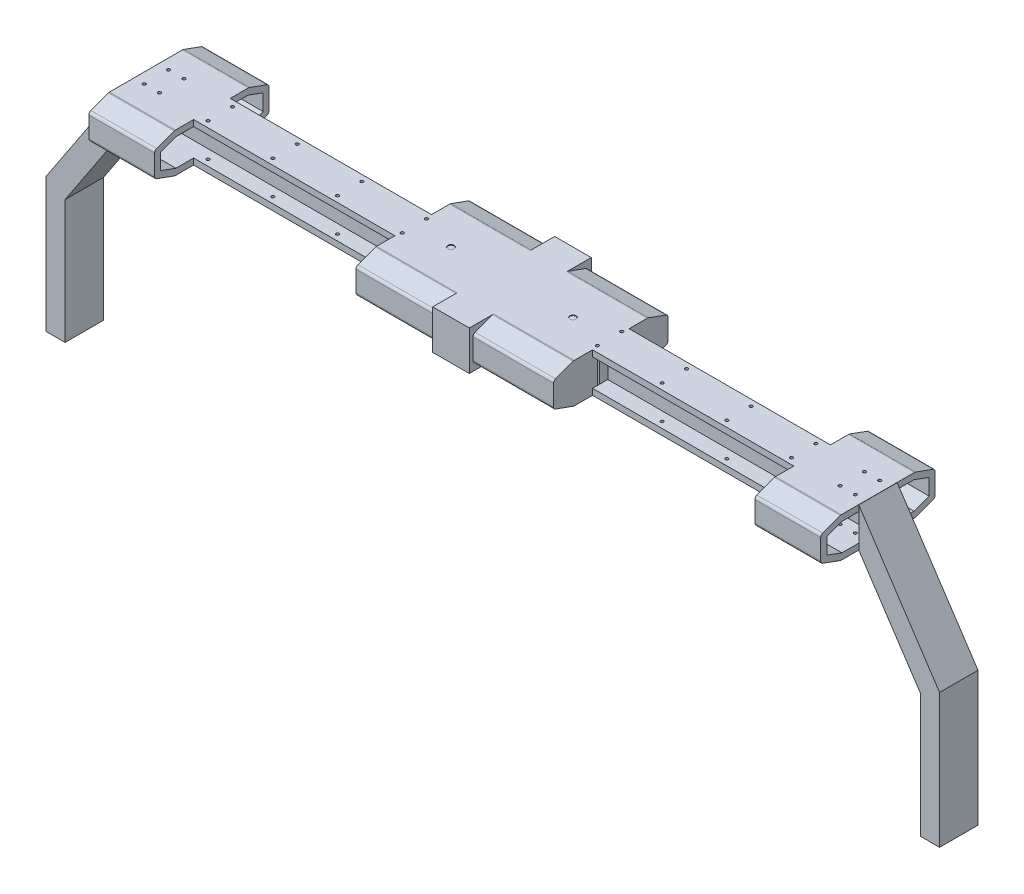
SolidWorks part; units mm, degrees
ref_plane "Alzado" through (0, 0, 0) normal (0, 0, 1) x (1, 0, 0)
ref_plane "Planta" through (0, 0, 0) normal (0, 1, 0) x (1, 0, 0)
ref_plane "Vista lateral" through (0, 0, 0) normal (1, 0, 0) x (0, 0, -1)
sketch "Sketch1" plane through (0, 0, 0) normal (1, 0, 0) x (0, 0, -1)
  line L0 (0, 0) -> (0, 59.5014) construction
  line L1 (0, 0) -> (-76.3871, 0) construction
  line L2 (30, 32.315) -> (-30, 32.315)
  line L3 (-30, 32.315) -> (-30, 22.315)
  line L4 (-30, 22.315) -> (-5, 22.315)
  line L5 (-5, 22.315) -> (-5, -22.315)
  line L6 (5, 22.315) -> (5, -22.315)
  line L7 (30, 22.315) -> (5, 22.315)
  line L8 (30, 32.315) -> (30, 22.315)
  line L9 (30, -32.315) -> (30, -22.315)
  line L10 (30, -22.315) -> (5, -22.315)
  line L11 (-30, -22.315) -> (-5, -22.315)
  line L12 (-30, -32.315) -> (-30, -22.315)
  line L13 (30, -32.315) -> (-30, -32.315)
  point P13 (0, 32.315)
  point P16 (5, 0)
  point P17 (-5, 0)
  point P19 (0, -32.315)
  dimension "D1" = 5
  dimension "D2" = 10
  dimension "D3" = 30
  dimension "D4" = 32.315
extrude "Boss-Extrude1" add sketch "Sketch1" along normal blind 600
sketch "Sketch10" plane through (0, 0, 0) normal (0, 1, 0) x (1, 0, 0)
  line L0 (0, 30) -> (0, -30) construction
  line L1 (0, 100) -> (30, 100)
  line L2 (0, 100) -> (0, -100)
  line L3 (0, -100) -> (30, -100)
  line L4 (30, 100) -> (30, -100)
  point P4 (30, 0)
  dimension "D1" = 30
  dimension "D2" = 200
extrude "Boss-Extrude5" add sketch "Sketch10" along normal mid plane 52
sketch "Sketch6" plane through (0, 32.315, 0) normal (0, 1, 0) x (1, 0, 0)
  line L0 (0, 30) -> (0, -30) construction
  line L1 (0, 100) -> (30, 100)
  line L2 (0, 100) -> (0, -100)
  line L3 (0, -100) -> (30, -100)
  line L4 (30, 100) -> (30, -100)
  point P4 (30, 0)
  dimension "D1" = 200
  dimension "D2" = 30
extrude "Boss-Extrude3" add sketch "Sketch6" against normal up to surface (64.63 mm away) up to face at (300, -32.315, 0)
ref_plane "Plane3" through (30, 0, 0) normal (1, 0, 0) x (0, 0, -1)
sketch "Sketch7" plane through (30, 0, 0) normal (1, 0, 0) x (0, 0, -1)
  line L0 (-30, -32.315) -> (30, -32.315) construction
  line L1 (0, 0) -> (58.0683, 0) construction
  line L2 (59.9268, 32.315) -> (-59.9268, 32.315)
  line L3 (93.88, -5.2694) -> (93.88, 16.7769)
  line L4 (90.5901, 21.4754) -> (61.6369, 32.0135)
  line L5 (90.5901, -21.4754) -> (61.6369, -32.0135)
  line L6 (93.88, 5.2694) -> (93.88, -16.7769)
  line L7 (59.9268, -32.315) -> (-59.9268, -32.315)
  line L8 (0, 0) -> (0, 18.5009) construction
  line L9 (-93.88, 5.2694) -> (-93.88, -16.7769)
  line L10 (-90.5901, -21.4754) -> (-61.6369, -32.0135)
  line L11 (-90.5901, 21.4754) -> (-61.6369, 32.0135)
  line L12 (-93.88, -5.2694) -> (-93.88, 16.7769)
  arc A0 (93.88, -16.7769) -> (90.5901, -21.4754) centre (88.88, -16.7769) cw
  arc A1 (59.9268, -32.315) -> (60.7951, -32.239) centre (59.9268, -27.315) ccw
  arc A2 (60.7951, -32.239) -> (61.6369, -32.0135) centre (60.6047, -29.845) ccw
  arc A3 (60.7951, 32.239) -> (61.6369, 32.0135) centre (60.6047, 29.845) cw
  arc A4 (59.9268, 32.315) -> (60.7951, 32.239) centre (59.9268, 27.315) cw
  arc A5 (93.88, 16.7769) -> (90.5901, 21.4754) centre (88.88, 16.7769) ccw
  arc A6 (-93.88, 16.7769) -> (-90.5901, 21.4754) centre (-88.88, 16.7769) cw
  arc A7 (-59.9268, 32.315) -> (-60.7951, 32.239) centre (-59.9268, 27.315) ccw
  arc A8 (-60.7951, 32.239) -> (-61.6369, 32.0135) centre (-60.6047, 29.845) ccw
  arc A9 (-60.7951, -32.239) -> (-61.6369, -32.0135) centre (-60.6047, -29.845) cw
  arc A10 (-59.9268, -32.315) -> (-60.7951, -32.239) centre (-59.9268, -27.315) cw
  arc A11 (-93.88, -16.7769) -> (-90.5901, -21.4754) centre (-88.88, -16.7769) ccw
  point P42 (0, -32.315)
  point P44 (0, 32.315)
  dimension "D1" = 0
extrude "Boss-Extrude4" add sketch "Sketch7" along normal blind 132 contours L9 A11 L10 A9 A10 L7 A1 A2 L5 A0 L6 L3 A5 L4 A3 A4 L2 A7 A8 L11 A6 L12 region at (30, 0, 0)
sketch "Sketch8" plane through (600, 0, 0) normal (1, 0, 0) x (0, 0, -1)
  line L0 (-30, -32.315) -> (30, -32.315) construction
  line B0 (0, 0) -> (58.0683, 0) construction
  line B1 (59.9268, 32.315) -> (-59.9268, 32.315)
  line B2 (93.88, -5.2694) -> (93.88, 16.7769)
  line B3 (90.5901, 21.4754) -> (61.6369, 32.0135)
  line B4 (90.5901, -21.4754) -> (61.6369, -32.0135)
  line B5 (93.88, 5.2694) -> (93.88, -16.7769)
  line B6 (59.9268, -32.315) -> (-59.9268, -32.315)
  line B7 (0, 0) -> (0, 18.5009) construction
  line B8 (-93.88, 5.2694) -> (-93.88, -16.7769)
  line B9 (-90.5901, -21.4754) -> (-61.6369, -32.0135)
  line B10 (-90.5901, 21.4754) -> (-61.6369, 32.0135)
  line B11 (-93.88, -5.2694) -> (-93.88, 16.7769)
  arc B12 (93.88, -16.7769) -> (90.5901, -21.4754) centre (88.88, -16.7769) cw
  arc B13 (59.9268, -32.315) -> (60.7951, -32.239) centre (59.9268, -27.315) ccw
  arc B14 (60.7951, -32.239) -> (61.6369, -32.0135) centre (60.6047, -29.845) ccw
  arc B15 (60.7951, 32.239) -> (61.6369, 32.0135) centre (60.6047, 29.845) cw
  arc B16 (59.9268, 32.315) -> (60.7951, 32.239) centre (59.9268, 27.315) cw
  arc B17 (93.88, 16.7769) -> (90.5901, 21.4754) centre (88.88, 16.7769) ccw
  arc B18 (-93.88, 16.7769) -> (-90.5901, 21.4754) centre (-88.88, 16.7769) cw
  arc B19 (-59.9268, 32.315) -> (-60.7951, 32.239) centre (-59.9268, 27.315) ccw
  arc B20 (-60.7951, 32.239) -> (-61.6369, 32.0135) centre (-60.6047, 29.845) ccw
  arc B21 (-60.7951, -32.239) -> (-61.6369, -32.0135) centre (-60.6047, -29.845) cw
  arc B22 (-59.9268, -32.315) -> (-60.7951, -32.239) centre (-59.9268, -27.315) cw
  arc B23 (-93.88, -16.7769) -> (-90.5901, -21.4754) centre (-88.88, -16.7769) ccw
sketch_block_instance "Block1-1"
sketch_block "Block1"
extrude "Extrude-Thin1" add sketch "Sketch8" against normal blind 108 thin thin type one direction wall 10
sketch "Sketch3" plane through (0, 0, 0) normal (0, 0, 1) x (1, 0, 0)
  line L0 (600, 32.0135) -> (732.5, -168.0959)
  line L1 (600, -32.315) -> (701.2415, -185.216)
  line L3 (600, 32.0135) -> (600, -32.315)
  line L5 (732.5, -168.0959) -> (732.5, -388.0959)
  line L6 (732.5, -388.0959) -> (701.2415, -388.0959)
  line L7 (701.2415, -388.0959) -> (701.2415, -185.216)
  line L10 (600, -13.2759) -> (600, -22.315) construction
  dimension "D1" = 732.5
  dimension "D2" = 240
  dimension "D3" = 220
extrude "Boss-Extrude2" add sketch "Sketch3" along normal mid plane 63
sketch "Sketch2" plane through (0, 32.315, 0) normal (0, 1, 0) x (1, 0, 0)
  line L0 (0, 100) -> (0, -100) construction
  line L2 (492, 30) -> (162, 30) construction
  line L3 (0, 0) -> (58.1974, 0) construction
  line L4 (600, 59.9268) -> (600, -59.9268) construction
  circle A0 centre (160, 20) radius 2.5
  circle A1 centre (160, -20) radius 2.5
  circle A2 centre (266.07, 20) radius 2.5
  circle A3 centre (266.07, -20) radius 2.5
  circle A4 centre (583, 20) radius 2.5
  circle A5 centre (558, 20) radius 2.5
  circle A6 centre (583, -20) radius 2.5
  circle A7 centre (558, -20) radius 2.5
  circle A8 centre (372.14, 20) radius 2.5
  circle A9 centre (372.14, -20) radius 2.5
  circle A10 centre (478.21, -20) radius 2.5
  circle A11 centre (478.21, 20) radius 2.5
  dimension "D1" = 5
  dimension "D2" = 106.07
  dimension "D3" = 160
  dimension "D5" = 25
  dimension "D6" = 10
  dimension "D7" = 106.07
  dimension "D8" = 106.07
  dimension "D4" = 17
extrude "Cut-Extrude1" cut sketch "Sketch2" against normal through all
sketch "Sketch12" plane through (0, 32.315, 0) normal (0, 1, 0) x (1, 0, 0)
  circle A0 centre (-100, 0) radius 5
  circle A1 centre (100, 0) radius 5
  dimension "D1" = 10
  dimension "D2" = 10
  dimension "D3" = 100
  dimension "D4" = 100
extrude "Cut-Extrude2" cut sketch "Sketch12" against normal blind 1
mirror "Mirror2" about plane through (0, 0, 0) normal (-1, 0, 0) of bodies 111 105
equation "\"separacion\"=106.07"
equation "\"D2@Sketch2\"=\"separacion\""
equation "\"D7@Sketch2\"=\"separacion\""
equation "\"D8@Sketch2\"=\"separacion\""
